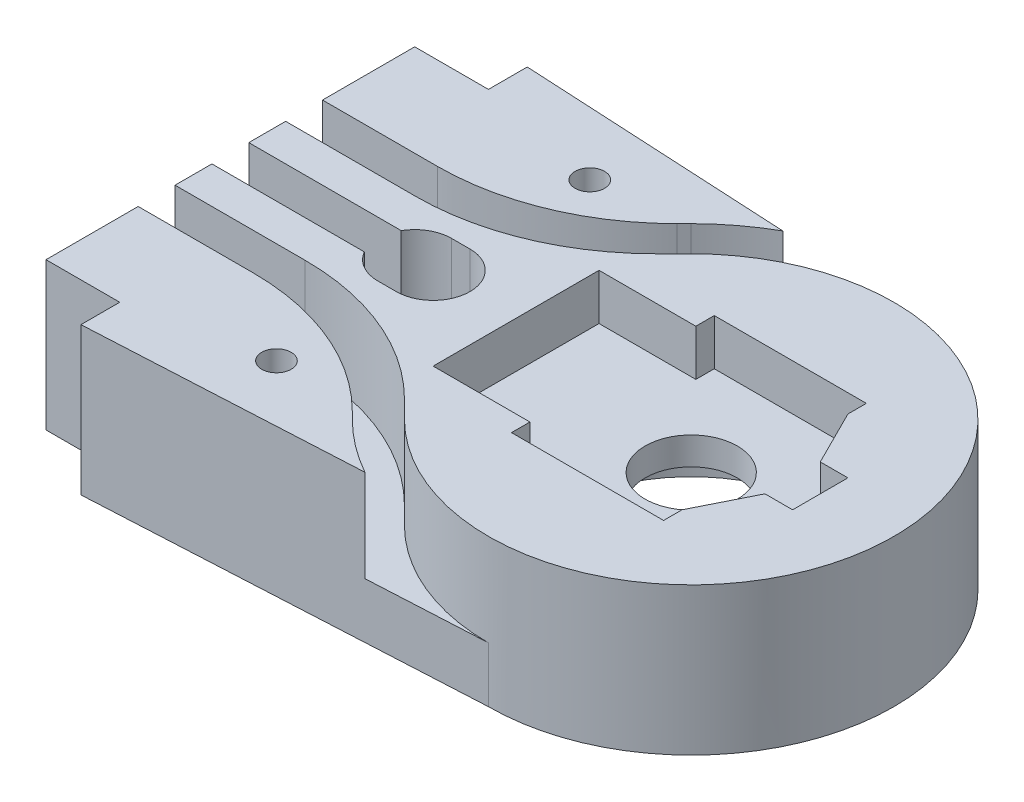
SolidWorks part; units mm, degrees
ref_plane "Front" through (0, 0, 0) normal (0, 0, 1) x (1, 0, 0)
ref_plane "Top" through (0, 0, 0) normal (0, 1, 0) x (1, 0, 0)
ref_plane "Right" through (0, 0, 0) normal (1, 0, 0) x (0, 0, -1)
sketch "Sketch1" plane through (0, 0, 0) normal (0, 1, 0) x (1, 0, 0)
  line L0 (0, 0) -> (38, 0) construction
  line L1 (13, 0) -> (13, 10)
  line L2 (13, 0) -> (13, -10)
  line L3 (13, -10) -> (33.4174, -10)
  line L4 (13, 10) -> (33.4174, 10)
  line L5 (0, 13) -> (38, 11)
  line L6 (0, -13) -> (38, -11)
  line L7 (13, 10) -> (17, 10) construction
  line L8 (17, 10) -> (17, 12.1053)
  line L9 (13, -10) -> (17, -10) construction
  line L10 (17, -10) -> (17, -12.1053)
  circle A0 centre (0, 0) radius 13
  circle A1 centre (38, 0) radius 11
  circle A2 centre (38, 0) radius 2.5
extrude "Boss-Extrude1" add sketch "Sketch1" along normal blind 8 contours A1 | L1 L0 A1 L4 | L0 L2 L3 A1 | A1 L3 L10 L6 | A1 L5 L8 L4 region at (21.0012, 0, 0) region at (25.2079, 0, -10.8517) region at (25.2079, 0, 10.8517) region at (35.7211, 0, -10.4431)
sketch "Sketch2" plane through (0, 0, 0) normal (0, 1, 0) x (1, 0, 0)
  line L0 (0, 0) -> (20, 0) construction
  line L3 (20, 0) -> (24, 0) construction
  line L4 (24, 0) -> (24, 8.5) construction
  line L5 (24, 0) -> (24, -8.5) construction
  circle A0 centre (24, 8.5) radius 0.8
  circle A1 centre (24, 0) radius 0.8
  circle A3 centre (24, -8.5) radius 0.8
extrude "Screw Holes" cut sketch "Sketch2" along normal through all
sketch "Sketch10" plane through (0, 0, 0) normal (0, 1, 0) x (1, 0, 0)
  circle A0 centre (24, 0) radius 1.25
extrude "Screw Heads" cut sketch "Sketch10" along normal blind 2
sketch "Sketch 3" plane through (0, 0, 0) normal (0, 1, 0) x (1, 0, 0)
  line L0 (38, 0) -> (30.2218, 7.7782) construction
  line L1 (38, 0) -> (30.2218, -7.7782) construction
  line L2 (0, 0) -> (38, 0) construction
  line L3 (19, 3) -> (19, 0) construction
  line L4 (19, 0) -> (19, -3) construction
  line L5 (19, 5) -> (13, 5)
  line L6 (30.2218, 7.7782) -> (28.8076, 9.1924) construction
  line L7 (13, 5) -> (13, 3)
  line L8 (13, 3) -> (19, 3)
  line L9 (19, -5) -> (13, -5)
  line L10 (19, -3) -> (20.0589, -3)
  line L11 (13, -5) -> (13, -3)
  line L12 (13, -3) -> (19, -3)
  line L13 (19, 3) -> (20.0589, 3)
  line L14 (29.2513, 6.8076) -> (30.2218, 7.7782)
  line L15 (29.2513, -6.8076) -> (30.2218, -7.7782)
  line L16 (30.2218, -7.7782) -> (28.8076, -9.1924) construction
  line L19 (31.6347, 11.335) -> (38, 11)
  line L20 (38, -11) -> (31.6347, -11.335)
  line L21 (19, -5) -> (19.2304, -5)
  line L23 (19, 5) -> (19.2304, 5)
  line L24 (28.4228, 8.8076) -> (28.8076, 9.1924)
  line L25 (28.4228, -8.8076) -> (28.8076, -9.1924)
  arc A0 (38, 11) -> (30.2218, 7.7782) centre (38, 0) ccw
  arc A1 (38, -11) -> (30.2218, -7.7782) centre (38, 0) cw
  arc A2 (28.8076, 9.1924) -> (31.6347, 11.335) centre (38, 0) cw
  arc A3 (28.8076, -9.1924) -> (31.6347, -11.335) centre (38, 0) ccw
  arc A4 (28.4228, 8.8076) -> (19.2304, 5) centre (19.2304, 18) cw
  arc A5 (20.0589, 3) -> (29.2513, 6.8076) centre (20.0589, 16) ccw
  arc A6 (29.2513, -6.8076) -> (20.0589, -3) centre (20.0589, -16) ccw
  arc A7 (28.4228, -8.8076) -> (19.2304, -5) centre (19.2304, -18) ccw
  dimension "D1" = 13
  dimension "D2" = 13
  dimension "D3" = 13
  dimension "D4" = 13
extrude "Distal/Middle Cable Canal" cut sketch "Sketch 3" against normal blind 5 from offset 8
sketch "Sketch3" plane through (28.2876, 0, 0) normal (0, 1, 0) x (1, 0, 0)
  line L26 (9.7124, 0) -> (16.7124, 0) construction
  line L27 (9.7124, 0) -> (0.2124, 0) construction
  line L28 (9.7124, 0) -> (9.7124, -5.5) construction
  line L29 (9.7124, 0) -> (9.7124, 5.5) construction
  line L30 (16.7124, 0) -> (16.7124, 1.5)
  line L31 (16.7124, 1.5) -> (15.2124, 1.5)
  line L32 (15.2124, 1.5) -> (13.7124, 1.5) construction
  line L33 (13.7124, 1.5) -> (13.7124, 4.5) construction
  line L34 (15.2124, 1.5) -> (13.7124, 4.5)
  line L35 (13.7124, 4.5) -> (13.7124, 5.5)
  line L36 (13.7124, 5.5) -> (9.7124, 5.5)
  line L37 (9.7124, 5.5) -> (5.4624, 5.5)
  line L38 (5.4624, 5.5) -> (5.4624, 4.5)
  line L39 (5.4624, 4.5) -> (0.2124, 4.5)
  line L40 (0.2124, 4.5) -> (0.2124, 0)
  line L41 (16.7124, 0) -> (16.7124, -1.5)
  line L42 (16.7124, -1.5) -> (15.2124, -1.5)
  line L43 (15.2124, -1.5) -> (13.7124, -1.5) construction
  line L44 (13.7124, -1.5) -> (13.7124, -4.5) construction
  line L45 (15.2124, -1.5) -> (13.7124, -4.5)
  line L46 (13.7124, -4.5) -> (13.7124, -5.5)
  line L47 (13.7124, -5.5) -> (9.7124, -5.5)
  line L48 (9.7124, -5.5) -> (5.4624, -5.5)
  line L49 (5.4624, -5.5) -> (5.4624, -4.5)
  line L50 (5.4624, -4.5) -> (0.2124, -4.5)
  line L51 (0.2124, -4.5) -> (0.2124, 0)
extrude "Pot Insert" cut sketch "Sketch3" against normal blind 2.5 from offset 8
sketch "Sketch5" plane through (0, 0, 0) normal (0, 1, 0) x (1, 0, 0)
  line L0 (13, 0) -> (13, 1)
  line L1 (13, 1) -> (21.2679, 1)
  line L2 (13, -1) -> (21.2679, -1)
  line L3 (13, 0) -> (13, -1)
  line L4 (23, 2) -> (24, 2)
  line L5 (23, -2) -> (24, -2)
  line L8 (21, 0) -> (23, 0) construction
  arc A0 (21, 0) -> (23, 2) centre (23, 0) cw
  arc A1 (24, 2) -> (24, -2) centre (24, 0) cw
  arc A2 (21, 0) -> (23, -2) centre (23, 0) ccw
extrude "Cut-Extrude1" cut sketch "Sketch5" along normal blind 5 from offset 3 contours L0 L3 | A0 A2 A1 region at (17.0438, 0, 0) region at (23.5, 0, 0)
sketch "Sketch7" plane through (0, 0, 0) normal (0, 1, 0) x (1, 0, 0)
  circle A0 centre (38, 0) radius 7.5
extrude "Cut-Extrude2" cut sketch "Sketch7" along normal blind 4
